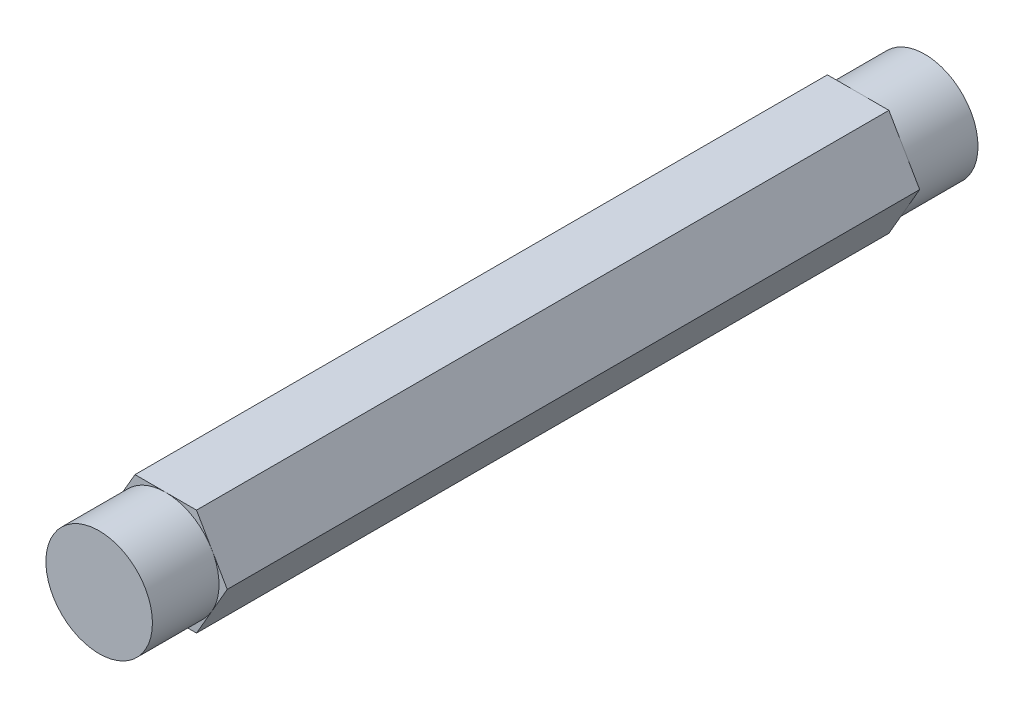
SolidWorks part; units mm, degrees
ref_plane "Front Plane" through (0, 0, 0) normal (0, 0, 1) x (1, 0, 0)
ref_plane "Top Plane" through (0, 0, 0) normal (0, 1, 0) x (1, 0, 0)
ref_plane "Right Plane" through (0, 0, 0) normal (1, 0, 0) x (0, 0, -1)
sketch "Sketch1" plane through (0, 0, 0) normal (0, 0, 1) x (1, 0, 0)
  line L1 (3.6662, 6.35) -> (-3.6662, 6.35)
  line L2 (-3.6662, 6.35) -> (-7.3323, 0)
  line L3 (-7.3323, 0) -> (-3.6662, -6.35)
  line L4 (-3.6662, -6.35) -> (3.6662, -6.35)
  line L5 (3.6662, -6.35) -> (7.3323, 0)
  line L6 (7.3323, 0) -> (3.6662, 6.35)
  circle A0 centre (0, 0) radius 6.35 construction
  point P1 (0, 6.35)
  dimension "D1" = 12.7
extrude "Boss-Extrude1" add sketch "Sketch1" along normal mid plane 98.425
sketch "Sketch2" plane through (0, 0, 49.2125) normal (0, 0, 1) x (1, 0, 0)
  circle A0 centre (0, 0) radius 6.35
  dimension "D1" = 12.7
extrude "Cut-Extrude1" cut sketch "Sketch2" against normal blind 7.9375 flip side to cut
mirror "Mirror1" about plane through (0, 0, 0) normal (0, 0, 1) of "Cut-Extrude1"
